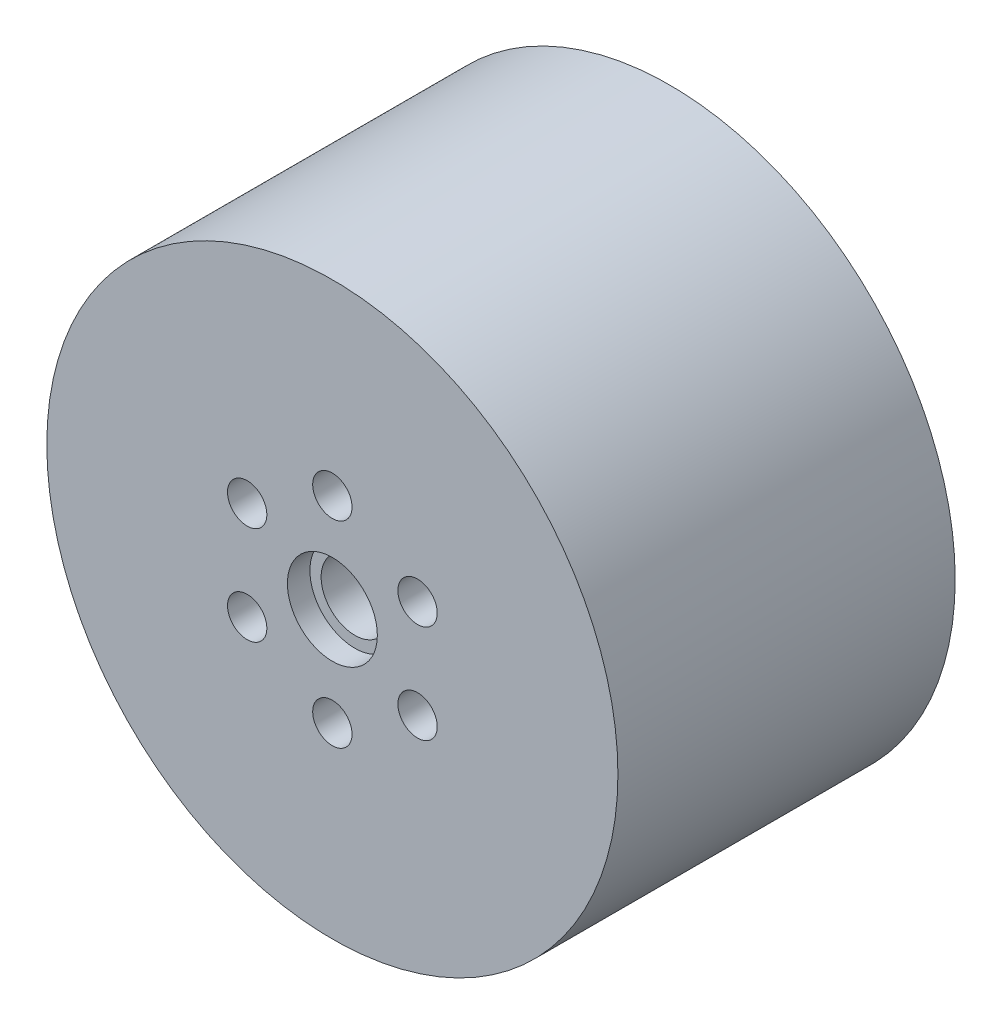
SolidWorks part; units mm, degrees
material "POLYURETHANE (11671)"
ref_plane "Front Plane" through (0, 0, 0) normal (0, 0, 1) x (1, 0, 0)
ref_plane "Top Plane" through (0, 0, 0) normal (0, 1, 0) x (1, 0, 0)
ref_plane "Right Plane" through (0, 0, 0) normal (1, 0, 0) x (0, 0, -1)
sketch "Sketch1" plane through (0, 0, 0) normal (0, 0, 1) x (1, 0, 0)
  circle A0 centre (0, 0) radius 25.4
  dimension "D1" = 50.8
extrude "Boss-Extrude1" add sketch "Sketch1" along normal blind 30
sketch "Sketch2" plane through (0, 0, 30) normal (0, 0, 1) x (1, 0, 0)
  circle A0 centre (0, 0) radius 3
  dimension "D1" = 6
extrude "Cut-Extrude1" cut sketch "Sketch2" against normal through all contours A0
sketch "Sketch3" plane through (0, 0, 30) normal (0, 0, 1) x (1, 0, 0)
  circle A0 centre (0, 0) radius 4
  dimension "D1" = 8
extrude "Cut-Extrude3" cut sketch "Sketch3" against normal blind 2
sketch "Sketch4" plane through (0, 0, 0) normal (0, 0, -1) x (-1, 0, 0)
  circle A0 centre (0, 0) radius 4
  point P3 (-14.1216, -5.4541)
  dimension "D1" = 8
extrude "Cut-Extrude4" cut sketch "Sketch4" against normal blind 2
sketch "Sketch5" plane through (0, 0, 30) normal (0, 0, 1) x (1, 0, 0)
  circle A0 centre (0, 8.75) radius 1.75
  point P2 (0, 0)
  dimension "D1" = 3.5
  dimension "D2" = 8.75
extrude "Cut-Extrude5" cut sketch "Sketch5" against normal blind 5
pattern_circular "CirPattern1" count 6 over 360 about axis through (0, 0, 30) along (0, 0, 1) of "Cut-Extrude5"
